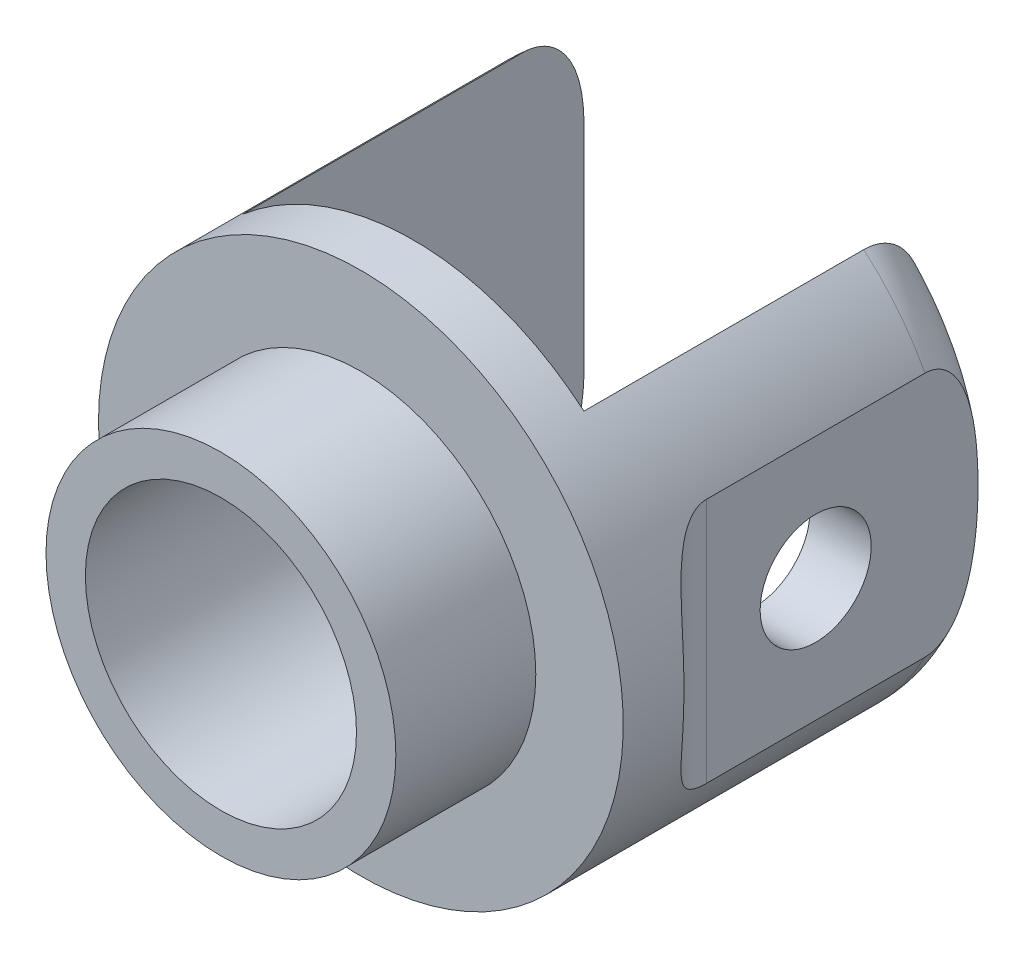
SolidWorks part; units mm, degrees
material "7075-T6 (SN)"
ref_plane "Front Plane" through (0, 0, 0) normal (0, 0, 1) x (1, 0, 0)
ref_plane "Top Plane" through (0, 0, 0) normal (0, 1, 0) x (1, 0, 0)
ref_plane "Right Plane" through (0, 0, 0) normal (1, 0, 0) x (0, 0, -1)
sketch "Sketch1" plane through (0, 0, 0) normal (0, 0, 1) x (1, 0, 0)
  circle A0 centre (0, 0) radius 10
  circle A1 centre (0, 0) radius 7.75
  dimension "D1" = 15.5
  dimension "D2" = 20
extrude "Boss-Extrude1" add sketch "Sketch1" along normal blind 8
sketch "Sketch2" plane through (0, 0, 0) normal (0, 0, -1) x (-1, 0, 0)
  circle A0 centre (0, 0) radius 7.75
  circle A1 centre (0, 0) radius 15
extrude "Boss-Extrude2" add sketch "Sketch2" along normal blind 22.5
sketch "Sketch3" plane through (0, 0, -22.5) normal (0, 0, -1) x (-1, 0, 0)
  line L0 (7.75, 0) -> (9.75, 0) construction
  line L1 (-7.75, 0) -> (-9.75, 0) construction
  line L2 (-9.75, -18.7961) -> (-9.75, 18.7961)
  line L5 (7.75, -18.7961) -> (-9.75, -18.7961)
  line L6 (-9.75, 18.7961) -> (9.75, 18.7961)
  line L7 (9.75, 18.7961) -> (9.75, -18.7961)
  line L8 (9.75, -18.7961) -> (7.75, -18.7961)
  circle A0 centre (0, 0) radius 7.75 construction
  point P10 (-9.75, 0)
extrude "Cut-Extrude1" cut sketch "Sketch3" against normal blind 19.5
sketch "Sketch4" plane through (0, 0, -22.5) normal (0, 0, -1) x (-1, 0, 0)
  line L0 (9.75, 0) -> (13.25, 0) construction
  line L1 (9.75, -11.399) -> (9.75, 11.399) construction
  line L2 (13.25, 0) -> (13.25, 9.8753)
  line L3 (13.25, 9.8753) -> (16.8223, 9.8753)
  line L4 (16.8223, 9.8753) -> (16.8223, -10.0622)
  line L5 (16.8223, -10.0622) -> (13.25, -10.0622)
  line L6 (13.25, -10.0622) -> (13.25, 0)
  line L7 (-9.75, 0) -> (-13.25, 0) construction
  line L8 (-9.75, 11.399) -> (-9.75, -11.399) construction
  line L9 (-13.25, 0) -> (-13.25, 9.8753)
  line L10 (-13.25, 9.8753) -> (-16.9469, 9.8753)
  line L11 (-16.9469, 9.8753) -> (-16.9469, -10.0622)
  line L12 (-16.9469, -10.0622) -> (-13.25, -10.0622)
  line L13 (-13.25, -10.0622) -> (-13.25, 0)
extrude "Cut-Extrude2" cut sketch "Sketch4" against normal blind 19.5
fillet "Fillet2" radius 3.5 2 edges at (-11.7055, -9.3798, -22.5) (11.7055, -9.3798, -22.5)
fillet "Fillet3" radius 3.5 2 edges at (13.25, 0, -3) (-13.25, 0, -3)
sketch "Sketch5" plane through (-13.25, 0, 0) normal (-1, 0, 0) x (0, 0, 1)
  line L0 (-3.4689, 0) -> (-22.0311, 0) construction
  circle A0 centre (-12.75, 0) radius 3.175
  spline S0 degree 3 poles (-6.5, 7.0312) (-6.3177, 7.0312) (-6.1407, 7.0047) (-5.7962, 6.9036) (-5.6347, 6.8304) (-5.1845, 6.559) (-4.9391, 6.3167) (-4.5292, 5.7728) (-4.3687, 5.4773) (-4.0995, 4.8539) (-3.9921, 4.5257) (-3.7298, 3.5303) (-3.6281, 2.8415) (-3.4964, 1.4266) (-3.4688, 0.7138) (-3.469, -0.7215) (-3.4969, -1.4308) (-3.5946, -2.4816) (-3.6368, -2.8297) (-3.7482, -3.5207) (-3.8175, -3.8636) (-3.9935, -4.5307) (-4.1012, -4.8585) (-4.3698, -5.4794) (-4.5298, -5.7732) (-4.936, -6.313) (-5.1851, -6.5594) (-5.6347, -6.8303) (-5.7941, -6.9026) (-6.1365, -7.0038) (-6.3175, -7.0312) (-6.5, -7.0312) knots 0 0 0 0 0.03125 0.03125 0.0625 0.0625 0.125 0.125 0.1875 0.1875 0.25 0.25 0.375 0.375 0.5 0.5 0.625 0.625 0.6875 0.6875 0.75 0.75 0.8125 0.8125 0.875 0.875 0.9375 0.9375 0.96875 0.96875 1 1 1 1 construction
  spline S1 degree 3 poles (-19, 7.0312) (-19.1769, 7.0312) (-19.3487, 7.0029) (-19.6834, 6.8955) (-19.8416, 6.8175) (-20.1356, 6.6261) (-20.2711, 6.513) (-20.5169, 6.2673) (-20.6287, 6.1336) (-20.9376, 5.7067) (-21.1005, 5.4007) (-21.375, 4.7635) (-21.486, 4.4301) (-21.7581, 3.4277) (-21.8644, 2.7488) (-22.0016, 1.3801) (-22.0312, 0.688) (-22.031, -0.6943) (-22.0014, -1.3825) (-21.8641, -2.7509) (-21.7578, -3.4314) (-21.4829, -4.4403) (-21.3726, -4.7703) (-21.0961, -5.4096) (-20.931, -5.717) (-20.6253, -6.1376) (-20.5123, -6.2725) (-20.2653, -6.5181) (-20.1316, -6.6291) (-19.8374, -6.8197) (-19.681, -6.8962) (-19.3521, -7.0019) (-19.1763, -7.0312) (-19, -7.0312) knots 0 0 0 0 0.03125 0.03125 0.0625 0.0625 0.09375 0.09375 0.125 0.125 0.1875 0.1875 0.25 0.25 0.375 0.375 0.5 0.5 0.625 0.625 0.75 0.75 0.8125 0.8125 0.875 0.875 0.90625 0.90625 0.9375 0.9375 0.96875 0.96875 1 1 1 1 construction
extrude "Cut-Extrude3" cut sketch "Sketch5" against normal blind 28
